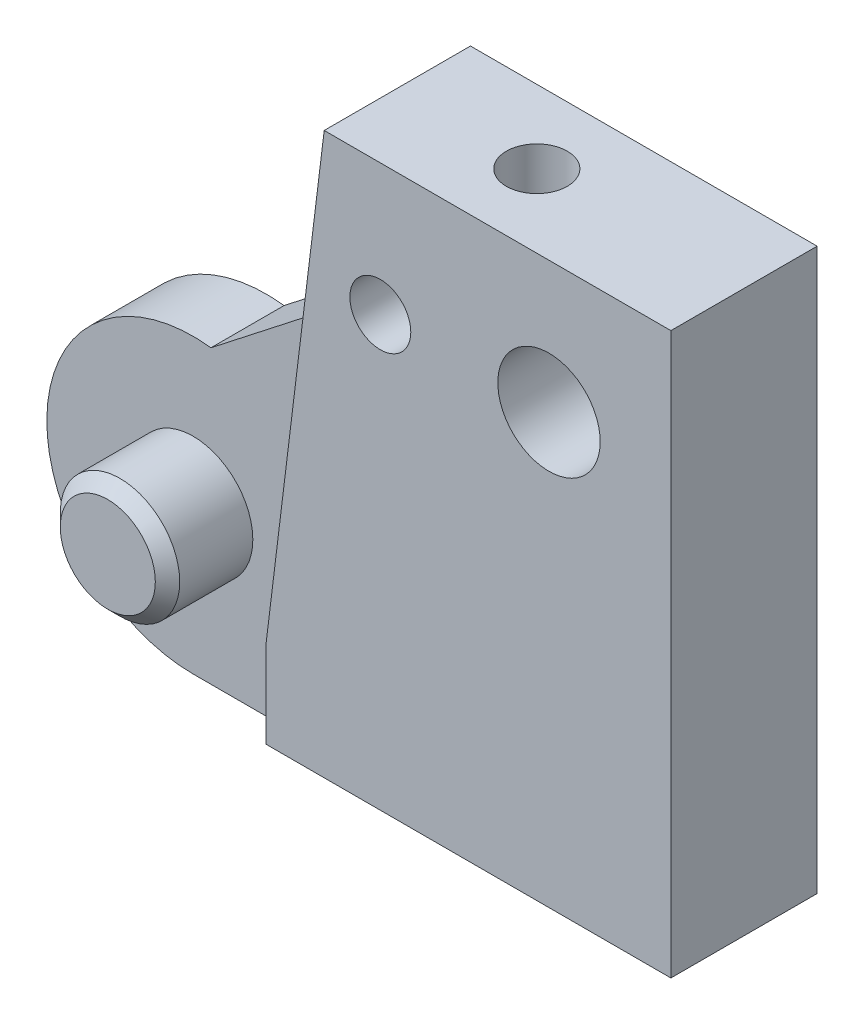
SolidWorks part; units mm, degrees
note: The reader was unsure of these and kept them because the rebuilt part matched: shared geometry of "Esboço1<3>".
ref_plane "Plano frontal" through (0, 0, 0) normal (0, 0, 1) x (1, 0, 0)
ref_plane "Plano superior" through (0, 0, 0) normal (0, 1, 0) x (1, 0, 0)
ref_plane "Plano direito" through (0, 0, 0) normal (1, 0, 0) x (0, 0, -1)
sketch "Esboço1" plane through (0, 0, 0) normal (0, 0, 1) x (1, 0, 0)
  line L0 (0, 0) -> (0, -2)
  line L1 (0, 0) -> (16.6, 0)
  line L2 (0, 0) -> (0, 23)
  line L3 (0, 23) -> (16.6, 23) construction
  line L5 (0, -2) -> (-6, -2)
  line L6 (-6, -2) -> (-6, 4) construction
  line L7 (-6, 10) -> (0, 10) construction
  line L8 (0, 10) -> (0, 16) construction
  line L13 (0, 23) -> (16.6, 23)
  line L14 (16.6, 0) -> (16.6, 23)
  line L15 (11.6, 23) -> (11.6, 17.6) construction
  circle A0 centre (-6, 4) radius 6 construction
  arc A1 (-6, -2) -> (-6, 10) centre (-6, 4) cw
  arc A2 (-6, 10) -> (0, 16) centre (-6, 16) ccw
  circle A6 centre (11.6, 17.6) radius 2
  circle A7 centre (4.68, 17.61) radius 0.5
  dimension "D13" = 4
  dimension "D17" = 1
  dimension "D1" = 16.6
  dimension "D2" = 23
  dimension "D3" = 6
  dimension "D4" = 2
  dimension "D5" = 6
  dimension "D6" = 6
  dimension "D12" = 5.4
  dimension "D14" = 5
  dimension "D15" = 4.68
  dimension "D16" = 5.39
extrude "Ressalto-extrusão1" add sketch "Esboço1" along normal blind 3 contours A2 A1 L5 L0 L2
extrude "Ressalto-extrusão2" add sketch "Esboço1<3>" along normal blind 6
sketch "Esboço1<3>" plane through (0, 0, 0) normal (0, 0, 1) x (1, 0, 0) same geometry as "Esboço1"
sketch "Esboço2" plane through (0, 0, 6) normal (0, 0, 1) x (1, 0, 0)
  line L0 (0, 0) -> (0, 23) construction
  line L1 (0, 23) -> (16.6, 23) construction
  line L2 (0, 0) -> (0, 23) construction
  line L3 (0, 23) -> (16.6, 23) construction
  line L4 (-0.0447, 3.2688) -> (2.378, 23) construction
  line L5 (0, 3.633) -> (2.378, 23)
  line L6 (2.378, 23) -> (0, 23)
  line L7 (0, 23) -> (0, 3.633)
  arc A0 (-6, 10) -> (-6, -2) centre (-6, 4) ccw construction
  arc A1 (-6, 10) -> (-6, -2) centre (-6, 4) ccw construction
  circle A2 centre (-6, 4) radius 6 construction
  dimension "D1" = 7
extrude "Corte-extrusão1" cut sketch "Esboço2" against normal blind 3
sketch "Esboço3" plane through (0, 0, 3) normal (0, 0, 1) x (1, 0, 0)
  line L0 (-5.2688, 9.9553) -> (0.6865, 9.2241)
  line L6 (-6, -2) -> (0, -2)
  line L7 (0, -2) -> (0, 0)
  line L8 (0, 0) -> (0, 3.633)
  line L9 (0, 3.633) -> (2.378, 23)
  line L10 (2.378, 23) -> (0, 23)
  line L11 (0, 23) -> (0, 16)
  line L12 (-6, -2) -> (0, -2)
  line L13 (0, -2) -> (0, 0)
  line L14 (0, 0) -> (0, 3.633)
  line L15 (0, 3.633) -> (2.378, 23)
  line L16 (2.378, 23) -> (0, 23)
  line L17 (0, 23) -> (0, 16)
  circle A0 centre (-6, 4) radius 6
  arc A2 (-6, 10) -> (0, 16) centre (-6, 16) ccw
  arc A3 (-6, 10) -> (-6, -2) centre (-6, 4) ccw
  arc A4 (-6, 10) -> (0, 16) centre (-6, 16) ccw
  arc A5 (-6, 10) -> (-6, -2) centre (-6, 4) ccw
  arc M9 (0, 16) -> (-6, 10) centre (-6, 16) cw
  line M14 (0, 3.633) -> (2.378, 23)
  line M15 (2.378, 23) -> (0, 23)
  line M16 (0, 23) -> (0, 16)
  dimension "D1" = 0
extrude "Corte-extrusão2" cut sketch "Esboço3" against normal through all contours A0 L0 M14 M15 M16 M9
chamfer "Chanfro1" distance 6 angle 45 2 edges at (0.6865, 9.2241, 1.5) (-2.2911, 9.5897, 0)
sketch "Esboço4" plane through (0, 0, 0) normal (0, -1, 0) x (1, 0, 0)
  line L0 (16.6, 3) -> (0, 3) construction
  line L1 (16.6, 6) -> (16.6, 0) construction
  point P5 (4, 3)
  point P6 (12.6, 3)
  dimension "D1" = 4
  dimension "D2" = 4
hole_wizard "Furo roscado de M3x0.51" positions "Esboço6" profile "Esboço5" tap size "M3x0.5" standard "Ansi Metric"
sketch "Esboço6" plane through (0, 0, 0) normal (0, -1, 0) x (1, 0, 0)
  point P0 (4, 3)
  point P3 (12.6, 3)
sketch "Esboço5" plane through (4, 0, 3) normal (1, 0, 0) x (0, 0, -1)
  line L0 (0, 0) -> (0, 9.2511)
  line L1 (0, 9.2511) -> (1.25, 8.5)
  line L2 (1.25, 8.5) -> (1.25, 0)
  line L5 (1.25, 0) -> (0, 0)
  line L10 (0, 9.2511) -> (-1.25, 8.5) construction
  line L11 (0, -6.35) -> (0, 107.95) construction
  dimension "Tap Drill Dia." = 2.5
  dimension "Tap Drill Depth" = 8.5
  dimension "Drill Angle" = 118
hole_wizard "Furo roscado de M3x0.52" positions "Esboço8" profile "Esboço7" tap size "M3x0.5" standard "Ansi Metric"
sketch "Esboço8" plane through (0, 0, 6) normal (0, 0, 1) x (1, 0, 0)
  point P0 (4.68, 17.61)
sketch "Esboço7" plane through (4.68, 17.61, 6) normal (1, 0, 0) x (0, -1, 0)
  line L0 (0, 0) -> (0, 6.7501)
  line L1 (0, 6.7501) -> (1.25, 5.999)
  line L2 (1.25, 5.999) -> (1.25, 0)
  line L5 (1.25, 0) -> (0, 0)
  line L10 (0, 6.7501) -> (-1.25, 5.999) construction
  line L11 (0, -6.35) -> (0, 107.95) construction
  dimension "Tap Drill Dia." = 2.5
  dimension "Tap Drill Depth" = 5.999
  dimension "Drill Angle" = 118
cosmetic thread "Rosca de furo1" parameters "D1"=6, "D2"=3
sketch "Esboço9" plane through (0, 23, 0) normal (0, 1, 0) x (1, 0, 0)
  line L0 (16.6, -3) -> (2.378, -3) construction
  line L1 (16.6, -6) -> (16.6, 0) construction
  line L2 (2.378, 0) -> (2.378, -6) construction
  point P6 (8.1, -3)
  dimension "D1" = 8.5
hole_wizard "Furo roscado de M3x0.53" positions "Esboço11" profile "Esboço10" tap size "M3x0.5" standard "Ansi Metric"
sketch "Esboço11" plane through (0, 23, 0) normal (0, 1, 0) x (1, 0, 0)
  point P0 (8.1, -3)
sketch "Esboço10" plane through (8.1, 23, 3) normal (1, 0, 0) x (0, 0, 1)
  line L0 (0, 0) -> (0, 3.7511)
  line L1 (0, 3.7511) -> (1.25, 3)
  line L2 (1.25, 3) -> (1.25, 0)
  line L5 (1.25, 0) -> (0, 0)
  line L10 (0, 3.7511) -> (-1.25, 3) construction
  line L11 (0, -6.35) -> (0, 107.95) construction
  dimension "Tap Drill Dia." = 2.5
  dimension "Tap Drill Depth" = 3
  dimension "Drill Angle" = 118
cosmetic thread "Rosca de furo2" parameters "D1"=3, "D2"=3
sketch "Esboço18" plane through (0, 0, 3) normal (0, 0, 1) x (1, 0, 0)
  arc A0 (-5.2688, 9.9553) -> (-6, -2) centre (-6, 4) ccw construction
  arc A1 (-5.2688, 9.9553) -> (-6, -2) centre (-6, 4) ccw construction
  circle A2 centre (-6, 4) radius 2.45
  dimension "D1" = 4.9
extrude "Ressalto-extrusão3" add sketch "Esboço18" along normal blind 3.5
chamfer "Chanfro2" distance 0.5 angle 45 1 edges at (-3.55, 4, 6.5)
hole_wizard "Furo roscado de M5x0.81" positions "Esboço20" profile "Esboço19" tap size "M5x0.8" standard "Ansi Metric"
sketch "Esboço20" plane through (0, 0, 6) normal (0, 0, 1) x (1, 0, 0)
  point P0 (11.6, 17.6)
sketch "Esboço19" plane through (11.6, 17.6, 6) normal (1, 0, 0) x (0, -1, 0)
  line L0 (0, 0) -> (0, 15.2618)
  line L1 (0, 15.2618) -> (2.1, 14)
  line L2 (2.1, 14) -> (2.1, 0)
  line L5 (2.1, 0) -> (0, 0)
  line L10 (0, 15.2618) -> (-2.1, 14) construction
  line L11 (0, -6.35) -> (0, 107.95) construction
  dimension "Tap Drill Dia." = 4.2
  dimension "Tap Drill Depth" = 14
  dimension "Drill Angle" = 118
cosmetic thread "Rosca de furo3" parameters "D1"=6, "D2"=5
